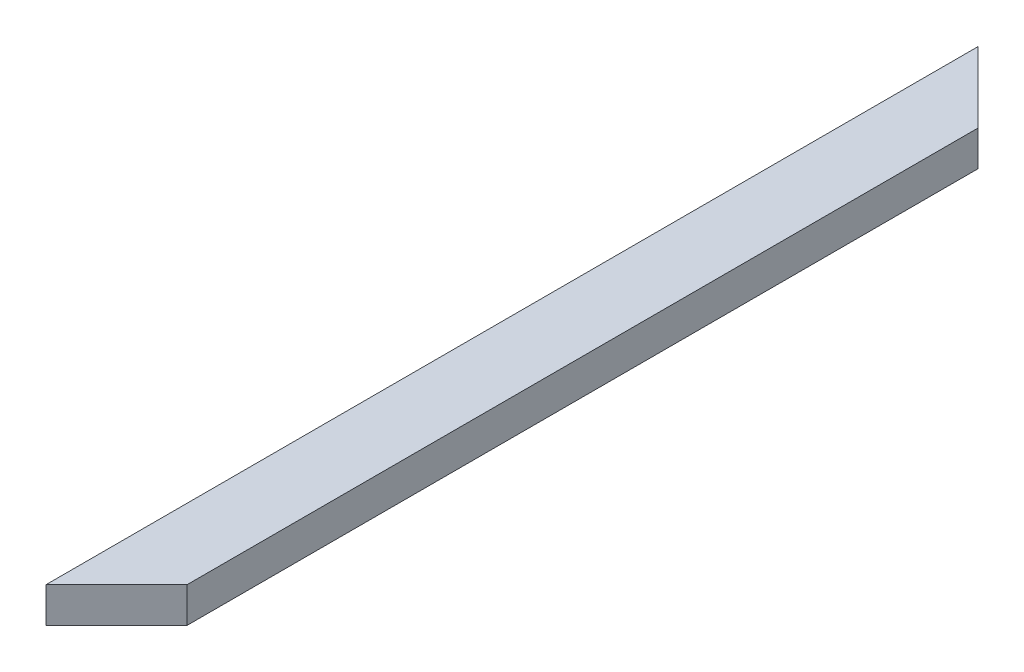
SolidWorks part; units mm, degrees
ref_plane "Front Plane" through (0, 0, 0) normal (0, 0, 1) x (1, 0, 0)
ref_plane "Top Plane" through (0, 0, 0) normal (0, 1, 0) x (1, 0, 0)
ref_plane "Right Plane" through (0, 0, 0) normal (1, 0, 0) x (0, 0, -1)
sketch "Sketch1" plane through (0, 0, 0) normal (0, 0, 1) x (1, 0, 0)
  line L1 (0, 0) -> (14, 0)
  line L2 (0, 0) -> (0, 7)
  line L3 (0, 7) -> (14, 7)
  line L4 (14, 0) -> (14, 7)
  dimension "D1" = 7
  dimension "D2" = 14
extrude "Boss-Extrude1" add sketch "Sketch1" along normal blind 185
sketch "Sketch2" plane through (0, 7, 0) normal (0, 1, 0) x (1, 0, 0)
  line L0 (0, 0) -> (14, -14)
  line L1 (14, -185) -> (14, 0) construction
  line L2 (14, -14) -> (14, 0)
  line L3 (14, 0) -> (0, 0)
  line L4 (0, -92.5) -> (14, -92.5) construction
  line L5 (0, -185) -> (0, 0) construction
  line L6 (14, -185) -> (0, -185)
  line L7 (14, -171) -> (14, -185)
  line L8 (0, -185) -> (14, -171)
  dimension "D1" = 45
extrude "Cut-Extrude1" cut sketch "Sketch2" against normal through all
